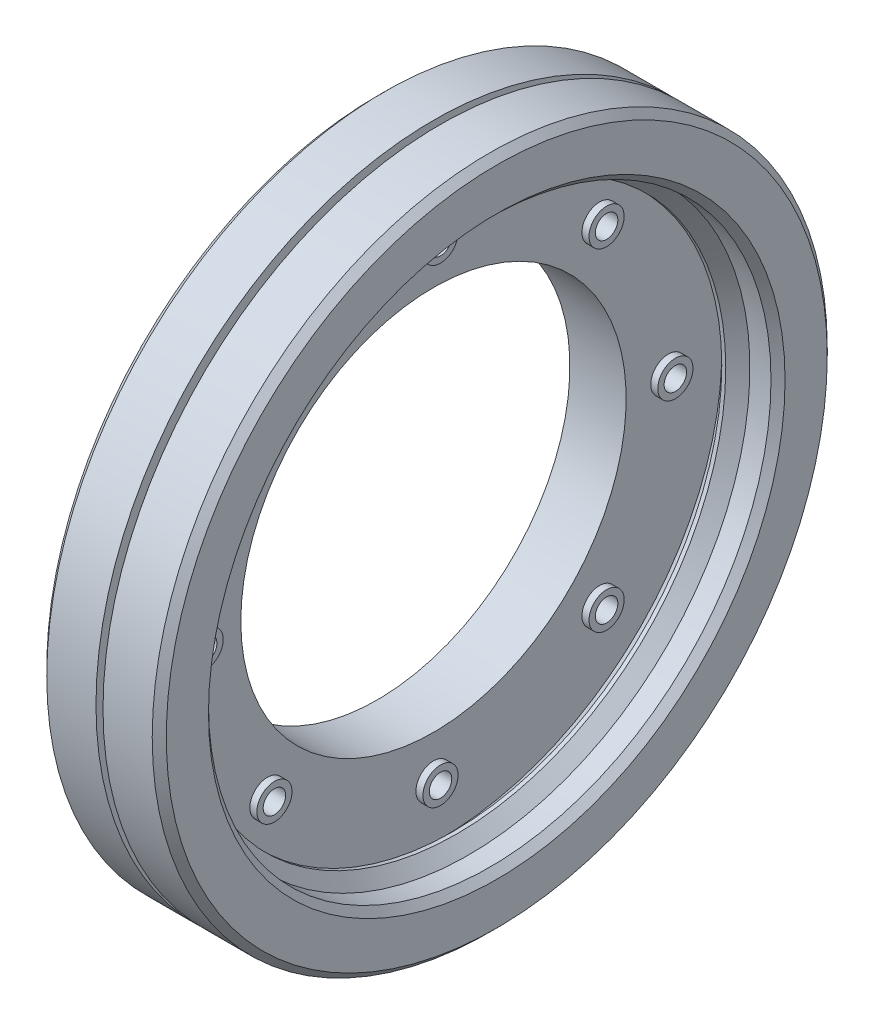
SolidWorks part; units mm, degrees
ref_plane "Front Plane" through (0, 0, 0) normal (0, 0, 1) x (1, 0, 0)
ref_plane "Top Plane" through (0, 0, 0) normal (0, 1, 0) x (1, 0, 0)
ref_plane "Right Plane" through (0, 0, 0) normal (1, 0, 0) x (0, 0, -1)
sketch "Sketch1" plane through (0, 0, 0) normal (0, 1, 0) x (1, 0, 0)
  line L0 (0, 40) -> (2, 38)
  line L1 (0, 48) -> (8, 48)
  line L2 (0, 48) -> (0, 40)
  line L3 (0, 40) -> (8, 40)
  line L4 (8, 48) -> (8, 40)
  line L5 (2, 38) -> (4, 40)
  line L6 (2, 33.4) -> (2, 38) construction
  line L7 (0, 27.4) -> (4, 27.4) construction
  line L8 (0, 27.4) -> (0, 39.4) construction
  line L9 (0, 39.4) -> (4, 39.4) construction
  line L10 (4, 27.4) -> (4, 39.4) construction
  line L11 (0, 27.4) -> (4, 39.4) construction
  line L12 (0, 39.4) -> (4, 27.4) construction
  line L13 (0, 0) -> (5.7592, 0)
  line L15 (-1, 48) -> (-9, 48)
  line L16 (-1, 48) -> (-1, 27.4)
  line L17 (-1, 27.4) -> (-9, 27.4)
  line L18 (-9, 48) -> (-9, 27.4)
  point P9 (2, 33.4)
  point P19 (0, 0)
  point P20 (0, 0)
  point P21 (0, 0)
  dimension "D1" = 40
  dimension "D2" = 45
  dimension "D3" = 4
  dimension "D4" = 8
  dimension "D5" = 8
  dimension "D6" = 12
  dimension "D7" = 4
  dimension "D8" = 1.4
  dimension "D9" = 1
  dimension "D10" = 8
revolve "Revolve1" add sketch "Sketch1" angle 360 about L13 region at (2, 0, -39.3333) region at (4, 0, -44)
revolve "Revolve2" add sketch "Sketch1<4>" angle 360 about L13 region at (-5, 0, -37.7)
sketch "Sketch1<4>" plane through (0, 0, 0) normal (0, 1, 0) x (1, 0, 0) same geometry as "Sketch1"
sketch "Sketch2" plane through (-1, 0, 0) normal (1, 0, 0) x (0, 0, -1)
  circle A0 centre (33.4, 0) radius 1.6
  circle A1 centre (33.4, 0) radius 2.5
  point P0 (33.4, 0)
  dimension "D1" = 3.2
  dimension "D2" = 5
extrude "Cut-Extrude1" cut sketch "Sketch2" against normal blind 10 contours A0
extrude "Boss-Extrude1" add sketch "Sketch2<3>" along normal blind 1
sketch "Sketch2<3>" plane through (-1, 0, 0) normal (1, 0, 0) x (0, 0, -1) same geometry as "Sketch2"
pattern_circular "CirPattern4" count 8 over 360 about axis through (0, 0, 0) along (-1, 0, 0) of "Cut-Extrude1", "Boss-Extrude1"
chamfer "Chamfer4" distance 0.4 angle 45 1 edges at (2, 0, 38)
chamfer "Chamfer5" distance 1 angle 45 2 edges at (8, 0, 48) (8, 0, 40)
chamfer "Chamfer6" distance 1 angle 45 1 edges at (-9, 0, 48)
